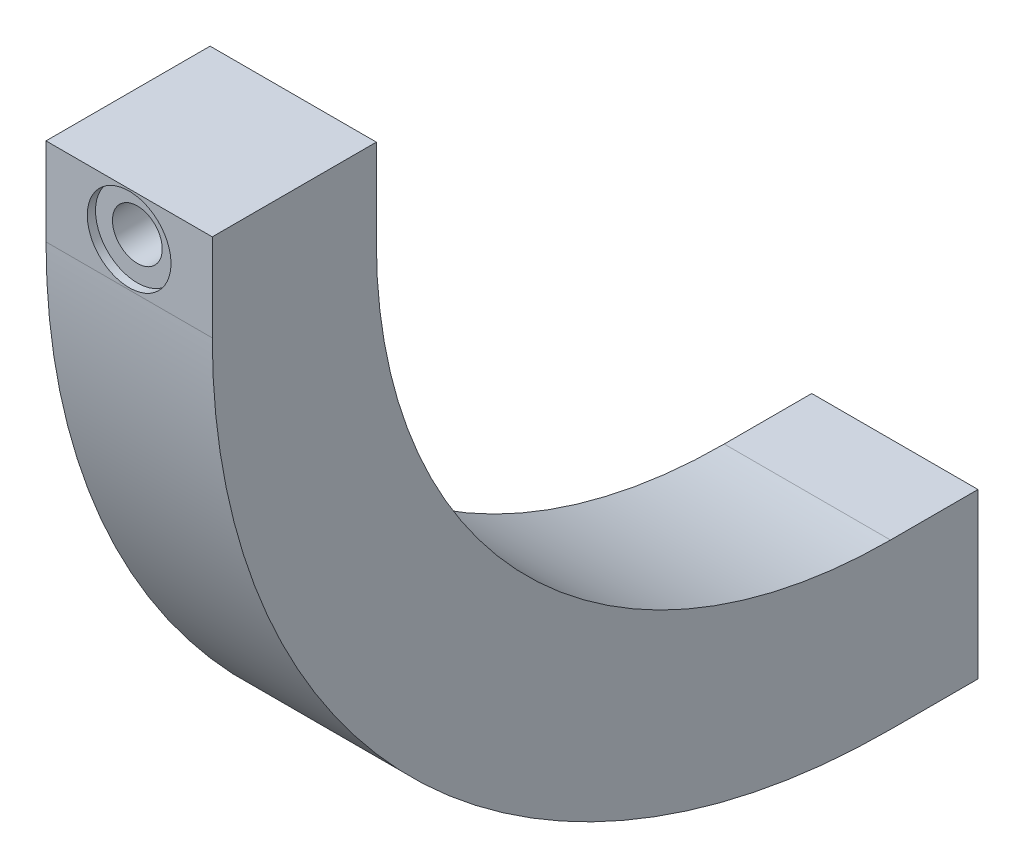
SolidWorks part; units mm, degrees
ref_plane "Front Plane" through (0, 0, 0) normal (0, 0, 1) x (1, 0, 0)
ref_plane "Top Plane" through (0, 0, 0) normal (0, 1, 0) x (1, 0, 0)
ref_plane "Right Plane" through (0, 0, 0) normal (1, 0, 0) x (0, 0, -1)
ref_axis "Z" through (0, 0, 22.75) along (0, 0, -1)
sketch "Sketch4" plane through (0, 0, 0) normal (0, 0, 1) x (1, 0, 0)
  circle A0 centre (0, 0) radius 50 construction
  dimension "D1" = 100
sketch "Sketch5" plane through (0, 0, 0) normal (1, 0, 0) x (0, 0, -1)
  line L0 (-51, 4) -> (-51, 0)
  line L1 (-51, 0) -> (-51, -4)
  line L2 (-66, -4) -> (-66, 4)
  line L6 (-66, 4) -> (-51, 4)
  line L12 (-22.75, 0) -> (-13.0351, 0) construction
  line L13 (0, 0) -> (-14.9091, -14.9091) construction
  line L14 (0, 0) -> (7.0065, 0) construction
  line L15 (0, -51) -> (-4, -51)
  line L16 (4, -51) -> (0, -51)
  line L17 (-4, -66) -> (4, -66)
  line L18 (4, -66) -> (4, -51)
  circle A0 centre (0, 0) radius 14 construction
  arc A1 (-51, -4) -> (-4, -51) centre (-4, -4) ccw
  arc A2 (-66, -4) -> (-4, -66) centre (-4, -4) ccw
  point P2 (9.4307, -21)
  point P4 (0, -2.1363)
  dimension "D1" = 28
  dimension "D4" = 4
  dimension "D2" = 45
  dimension "D3" = 15
  dimension "D5" = 51
sketch "Sketch6" plane through (0, 0, 0) normal (0, 1, 0) x (1, 0, 0)
  circle A0 centre (0, 0) radius 50 construction
  dimension "D1" = 100
extrude "Boss-Extrude1" add sketch "Sketch5" along normal blind 7.6 and the other way blind 7.6
sketch "Sketch7" plane through (0, 0, 0) normal (0, 0, 1) x (1, 0, 0)
  circle A0 centre (0, 0) radius 1.75
  dimension "D1" = 3.5
extrude "Cut-Extrude1" cut sketch "Sketch7" along normal through all
ref_axis "Y" through (0, -9.3489, 0) along (0, -1, 0)
sketch "Sketch12" plane through (0, 0, 66) normal (0, 0, 1) x (1, 0, 0)
  circle A0 centre (0, 0) radius 2.275
  dimension "D1" = 4.55
extrude "Cut-Extrude7" cut sketch "Sketch12" against normal blind 6
sketch "Sketch14" plane through (0, 0, 66) normal (0, 0, -1) x (1, 0, 0)
  circle A0 centre (0, 0) radius 3.825
  dimension "D1" = 7.65
extrude "Cut-Extrude10" cut sketch "Sketch14" along normal blind 0.75
sketch "Sketch16" plane through (0, 0, 0) normal (1, 0, 0) x (0, 0, -1)
  line L0 (0, -67) -> (0, 0) construction
  dimension "D1" = 67
ref_plane "Plane1" through (0, -67, 0) normal (0, 1, 0) x (1, 0, 0)
ref_axis "CX" through (0, -67, 4.4) along (0, 0, -1)
ref_plane "Plane2" through (0, 0, 0) normal (0, 0, -1) x (0, 1, 0)
ref_plane "Plane3" through (0, 0, 0) normal (1, 0, 0) x (0, 0, -1)
ref_axis "CZ" through (0, -8.7018, 0) along (0, -1, 0)
ref_axis "CY" through (-0.6471, -67, 0) along (1, 0, 0)
ref_point "CO"
sketch "Sketch15" plane through (0, -66, 0) normal (0, -1, 0) x (1, 0, 0)
  circle A0 centre (0, 0) radius 1.5
  dimension "D1" = 3
extrude "Cut-Extrude11" cut sketch "Sketch15" against normal blind 6
equation "\"rbracket-width\"= \"L2Thickness\" + 0.2"
equation "\"EyeCaptureRadius\"= ( \"EyeDiameter\" + \"EyeClearance\" ) / 2"
equation "\"rbracket_planetocenterline_dist\"= \"BasePlaneDistance\""
equation "\"EyeDiameter\" = 100"
equation "\"BasePlaneDistance\" = \"EyeDiameter\"/2+\"L2Thickness\"+\"EyeClearance\""
equation "\"EyeClearance\" = 2"
equation "\"D1@Sketch4\"=\"EyeDiameter\""
equation "\"D1@Sketch6\"=\"EyeDiameter\""
equation "\"D1@Boss-Extrude1\"=\"rbracket-width\"/2"
equation "\"D2@Boss-Extrude1\"=\"rbracket-width\"/2"
equation "\"L2Thickness\" = 15"
equation "\"D3@Sketch5\"=\"L2Thickness\""
equation "\"D5@Sketch5\"=(\"EyeDiameter\"+\"EyeClearance\")/2"
equation "\"BearingThickness\"= 6"
equation "\"BearingOD\"=4.5"
equation "\"OuterBearingProudDistance\"= 0"
equation "\"D1@Cut-Extrude7\"=\"BearingThickness\"-\"OuterBearingProudDistance\""
equation "\"D1@Sketch12\"= \"BearingOD\" + \"PrinterFilamentThickness\" *\"ApplyPrinterOffset\" / 2"
equation "\"FlangeOD\"=7.5"
equation "\"FlangeThickness\"= 0.75"
equation "\"D1@Sketch14\"=\"FlangeOD\" + \"PrinterFilamentThickness\"*1.5 * \"ApplyPrinterOffset\""
equation "\"D1@Cut-Extrude10\"=\"FlangeThickness\""
equation "\"PrinterFilamentThickness\"= 0.1'For setting distances for things like pressfits"
equation "\"ApplyPrinterOffset\"= 1'Set to 0 for line-to-line. Set to 1 for applying guestimate dimensions to make the printer produce good parts"
equation "\"D1@Cut-Extrude11\"=3*1.5"
equation "\"D1@Sketch16\"=\"BasePlaneDistance\""
